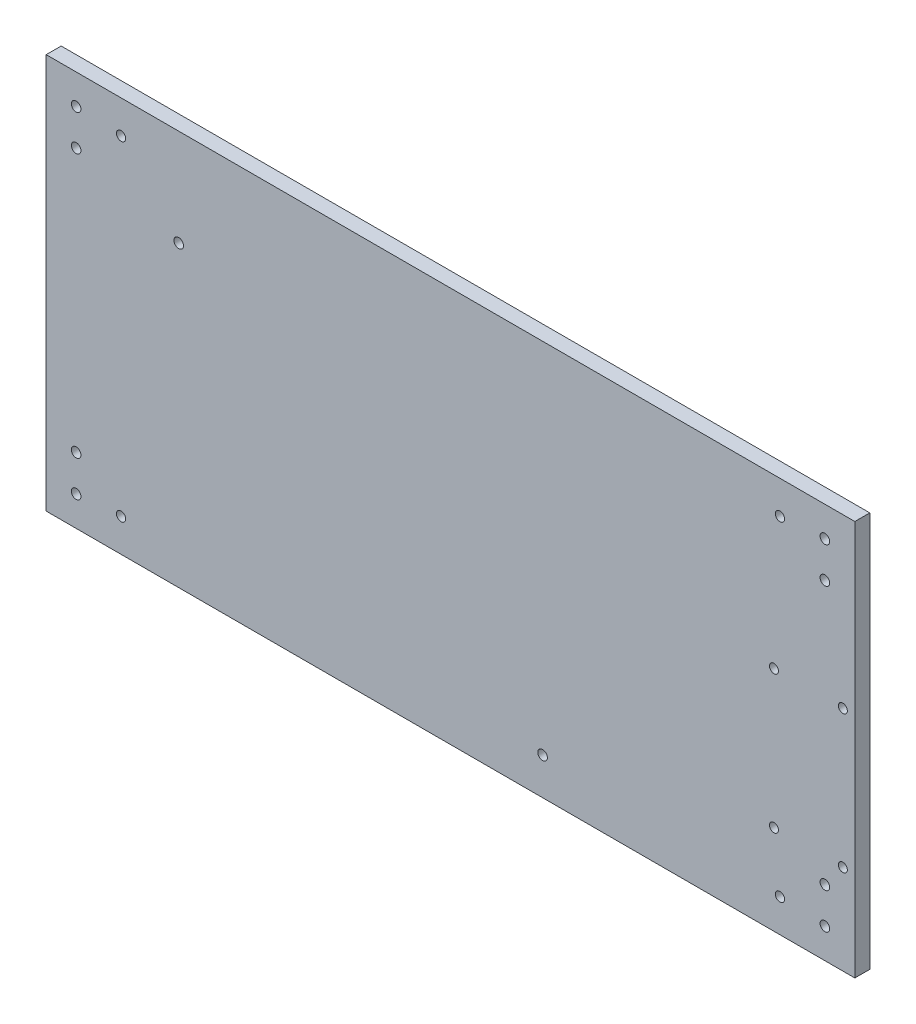
SolidWorks part; units mm, degrees
ref_plane "Front Plane" through (0, 0, 0) normal (0, 0, 1) x (1, 0, 0)
ref_plane "Top Plane" through (0, 0, 0) normal (0, 1, 0) x (1, 0, 0)
ref_plane "Right Plane" through (0, 0, 0) normal (1, 0, 0) x (0, 0, -1)
sketch "Sketch1" plane through (0, 0, 0) normal (0, 0, 1) x (1, 0, 0)
  line L1 (135, -66) -> (-135, -66)
  line L2 (135, -66) -> (135, 66)
  line L3 (135, 66) -> (-135, 66)
  line L4 (-135, -66) -> (-135, 66)
  line L5 (135, -66) -> (-135, 66) construction
  line L6 (135, 66) -> (-135, -66) construction
  point P0 (0, 0)
  dimension "D1" = 270
  dimension "D2" = 132
extrude "Base" add sketch "Sketch1" along normal mid plane 5 contours L4 L1 L2 L3 region at (0, 0, 0)
sketch "Sketch3" plane through (0, 0, -2.5) normal (0, 0, -1) x (-1, 0, 0)
  line L3 (90.75, -53.65) -> (-30.75, -53.65) construction
  line L4 (90.75, -53.65) -> (90.75, 33.65) construction
  line L5 (90.75, 33.65) -> (-30.75, 33.65) construction
  line L6 (-30.75, -53.65) -> (-30.75, 33.65) construction
  line L7 (90.75, -53.65) -> (-30.75, 33.65) construction
  line L8 (90.75, 33.65) -> (-30.75, -53.65) construction
  circle A0 centre (-30.75, -53.65) radius 1.6
  circle A1 centre (90.75, 33.65) radius 1.6
  point P2 (30, -10)
  dimension "D3" = 3.2
  dimension "D1" = 121.5
  dimension "D2" = 87.3
  dimension "D4" = 10
  dimension "D5" = 30
extrude "PSUMount" cut sketch "Sketch3" against normal through all
sketch "Sketch4" plane through (0, 0, 2.5) normal (0, 0, 1) x (1, 0, 0)
  line L1 (131, 10) -> (108, 10) construction
  line L2 (131, 10) -> (131, -36) construction
  line L3 (131, -36) -> (108, -36) construction
  line L4 (108, 10) -> (108, -36) construction
  line L5 (131, 10) -> (108, -36) construction
  line L6 (131, -36) -> (108, 10) construction
  line L7 (135, -66) -> (135, 66) construction
  circle A0 centre (108, 10) radius 1.5
  circle A1 centre (131, 10) radius 1.5
  circle A2 centre (108, -36) radius 1.5
  circle A3 centre (131, -36) radius 1.5
  point P0 (119.5, -13)
  point P16 (135, 0)
  dimension "D5" = 3
  dimension "D1" = 46
  dimension "D2" = 23
  dimension "D3" = 4
  dimension "D4" = 13
extrude "InterfaceHoles" cut sketch "Sketch4" against normal through all
sketch "Sketch5" plane through (0, 0, 2.5) normal (0, 0, 1) x (1, 0, 0)
  line L1 (110, -55) -> (-110, -55) construction
  line L2 (110, -55) -> (110, 55) construction
  line L3 (110, 55) -> (-110, 55) construction
  line L4 (-110, -55) -> (-110, 55) construction
  line L5 (110, -55) -> (-110, 55) construction
  line L6 (110, 55) -> (-110, -55) construction
  circle A0 centre (-110, -55) radius 1.55
  circle A1 centre (-110, 55) radius 1.55
  circle A2 centre (110, 55) radius 1.55
  circle A3 centre (110, -55) radius 1.55
  point P8 (0, 0)
  dimension "D1" = 3.1
  dimension "D2" = 110
  dimension "D3" = 220
extrude "Cut-Extrude2" cut sketch "Sketch5" against normal through all
hole_wizard "Ø3.2 (3.2) WallMountHoles" positions "Sketch6" profile "Sketch7" hole size "Ø3.2" standard "ANSI Metric" end condition through all
sketch "Sketch6" plane through (0, 0, 2.5) normal (0, 0, 1) x (1, 0, 0)
  line L0 (135, 66) -> (-135, 66) construction
  line L1 (-135, -66) -> (-135, 66) construction
  line L4 (135, -66) -> (135, 66) construction
  line L5 (135, -66) -> (-135, -66) construction
  point P0 (-125, 56)
  point P2 (-125, 44)
  point P4 (-125, -44)
  point P6 (-125, -56)
  point P8 (125, -56)
  point P10 (125, -44)
  point P12 (125, 44)
  point P14 (125, 56)
  dimension "D1" = 10
  dimension "D2" = 22
  dimension "D4" = 10
  dimension "D3" = 10
  dimension "D5" = 10
  dimension "D6" = 22
sketch "Sketch7" plane through (-125, 56, 2.5) normal (1, 0, 0) x (0, -1, 0)
  line L0 (0, 0) -> (0, 5)
  line L1 (0, 5) -> (1.6, 5)
  line L2 (1.6, 5) -> (1.6, 0)
  line L5 (1.6, 0) -> (0, 0)
  line L11 (0, -6.35) -> (0, 107.95) construction
  dimension "Thru Hole Dia." = 3.2
  dimension "Thru Hole Depth" = 5
equation "\"D3@Sketch6\"=\"D4@Sketch6\""
equation "\"D5@Sketch6\"=\"D1@Sketch6\""
equation "\"D6@Sketch6\"=\"D2@Sketch6\""
